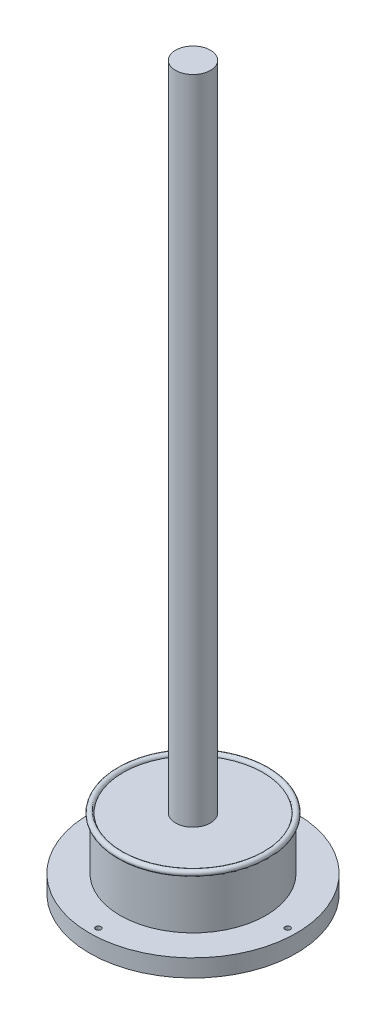
SolidWorks part; units mm, degrees
ref_plane "Front Plane" through (0, 0, 0) normal (0, 0, 1) x (1, 0, 0)
ref_plane "Top Plane" through (0, 0, 0) normal (0, 1, 0) x (1, 0, 0)
ref_plane "Right Plane" through (0, 0, 0) normal (1, 0, 0) x (0, 0, -1)
sketch "Sketch1" plane through (0, 0, 0) normal (0, 1, 0) x (1, 0, 0)
  circle A0 centre (0, 0) radius 39.75
  dimension "D1" = 79.5
extrude "Boss-Extrude1" add sketch "Sketch1" along normal blind 28.575
sketch "Sketch2" plane through (0, 28.575, 0) normal (0, 1, 0) x (1, 0, 0)
  circle A0 centre (0, 0) radius 9.525
  dimension "D1" = 19.05
extrude "Boss-Extrude2" add sketch "Sketch2" along normal blind 355.6
sketch "Sketch3" plane through (0, 0, 0) normal (0, -1, 0) x (1, 0, 0)
  circle A0 centre (0, 0) radius 56.388
  dimension "D1" = 112.776
extrude "Boss-Extrude3" add sketch "Sketch3" along normal blind 9.525
chamfer "Chamfer1" distance 1.27 angle 45 1 edges at (0, 28.575, 39.75)
sketch "Sketch5" plane through (0, 0, 0) normal (0, 0, 1) x (1, 0, 0)
  line L0 (38.48, 28.575) -> (-38.48, 28.575) construction
  line L1 (-39.75, 27.305) -> (-39.75, 0) construction
  circle A0 centre (-39.75, 28.575) radius 1.5875
  point P2 (0, 0)
  point P5 (0, 0)
  dimension "D1" = 3.175
ref_axis "Axis1" through (0, 384.175, 0) along (0, -1, 0)
revolve "Revolve1" add sketch "Sketch5" angle 360 about axis through (0, 384.175, 0) along (0, -1, 0)
hole_wizard "Tap Drill for #4-40 Tap1" positions "Sketch9" profile "Sketch10" hole size "#4-40" standard "ANSI Inch" end condition through all
sketch "Sketch9" plane through (0, 0, 0) normal (0, 1, 0) x (1, 0, 0)
  circle A0 centre (0, 0) radius 51.6255 construction
  point P0 (0, 51.6255)
  point P2 (51.6255, 0)
  point P4 (0, -51.6255)
  point P6 (-51.6255, 0)
  point P13 (0, 0)
  point P14 (0, 0)
  point P15 (0, 0)
  point P16 (0, 0)
  point P17 (0, 0)
  point P18 (0, 0)
  point P19 (0, 0)
  point P20 (0, 0)
  dimension "D1" = 103.251
sketch "Sketch10" plane through (0, 0, -51.6255) normal (1, 0, 0) x (0, 0, 1)
  line L0 (0, 0) -> (0, 9.525)
  line L1 (0, 9.525) -> (1.4351, 9.525)
  line L2 (1.4351, 9.525) -> (1.4351, 0)
  line L5 (1.4351, 0) -> (0, 0)
  line L11 (0, -6.35) -> (0, 107.95) construction
  dimension "Thru Hole Dia." = 2.8702
  dimension "Thru Hole Depth" = 9.525
